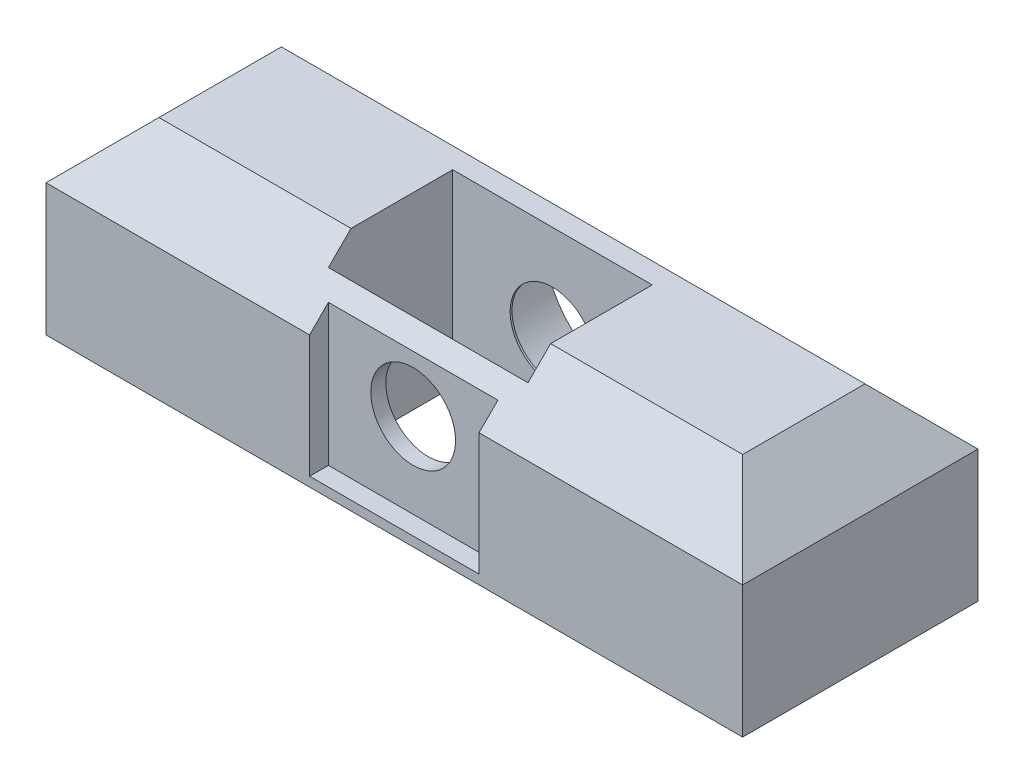
SolidWorks part; units mm, degrees
ref_plane "정면" through (0, 0, 0) normal (0, 0, 1) x (1, 0, 0)
ref_plane "윗면" through (0, 0, 0) normal (0, 1, 0) x (1, 0, 0)
ref_plane "우측면" through (0, 0, 0) normal (1, 0, 0) x (0, 0, -1)
sketch "스케치1" plane through (0, 0, 0) normal (0, 0, 1) x (1, 0, 0)
  line L1 (-18.5, 5) -> (18.5, 5)
  line L2 (-18.5, 5) -> (-18.5, -5)
  line L3 (-18.5, -5) -> (18.5, -5)
  line L4 (18.5, 5) -> (18.5, -5)
  line L5 (-18.5, 5) -> (18.5, -5) construction
  line L6 (-18.5, -5) -> (18.5, 5) construction
  point P0 (0, 0)
  dimension "D1" = 37
  dimension "D2" = 10
extrude "보스-돌출1" add sketch "스케치1" along normal blind 4.5
sketch "스케치4" plane through (0, 0, 4.5) normal (0, 0, 1) x (1, 0, 0)
  line L0 (-18.5, -5) -> (18.5, -5) construction
  line L1 (-18.5, 5) -> (-5.1, 5)
  line L2 (-18.5, 5) -> (-18.5, -5)
  line L3 (-18.5, -5) -> (-5.1, -5)
  line L4 (-5.1, 5) -> (-5.1, -5)
  line L5 (18.5, 5) -> (-18.5, 5) construction
  line L6 (18.5, 5) -> (5.1, 5)
  line L7 (18.5, 5) -> (18.5, -5)
  line L8 (18.5, -5) -> (5.1, -5)
  line L9 (5.1, 5) -> (5.1, -5)
  line L10 (18.5, -5) -> (18.5, 5) construction
  dimension "D1" = 10.2
  dimension "D2" = 5.1
extrude "보스-돌출2" add sketch "스케치4" along normal blind 6
sketch "스케치5" plane through (0, 0, 4.5) normal (0, 0, 1) x (1, 0, 0)
  line L1 (-5.1, -5) -> (5.1, -5)
  line L2 (-5.1, -5) -> (-5.1, 5)
  line L3 (-5.1, 5) -> (5.1, 5)
  line L4 (5.1, -5) -> (5.1, 5)
extrude "컷-돌출4" cut sketch "스케치5" against normal blind 0.2
sketch "스케치6" plane through (0, 0, 10.5) normal (0, 0, 1) x (1, 0, 0)
  line L1 (18.5, 5) -> (-18.5, 5)
  line L2 (18.5, 5) -> (18.5, -5)
  line L3 (18.5, -5) -> (-18.5, -5)
  line L4 (-18.5, 5) -> (-18.5, -5)
extrude "보스-돌출3" add sketch "스케치6" along normal blind 2
sketch "스케치2" plane through (0, 0, 0) normal (0, 0, 1) x (1, 0, 0)
  line L1 (-5.1, -5) -> (5.1, -5) construction
  circle A0 centre (0, 0) radius 2.25
  dimension "D1" = 5
  dimension "D2" = 4.5
extrude "컷-돌출1" cut sketch "스케치2" along normal through all
sketch "스케치3" plane through (0, 0, 0) normal (0, 0, -1) x (-1, 0, 0)
  circle A0 centre (0, 0) radius 4.5
extrude "컷-돌출3" cut sketch "스케치3" against normal blind 4
sketch "스케치7" plane through (0, 0, 12.5) normal (0, 0, 1) x (1, 0, 0)
  line L8 (-4.5, 4.5) -> (4.5, 4.5)
  line L9 (-4.5, 4.5) -> (-4.5, -4.5)
  line L10 (-4.5, -4.5) -> (4.5, -4.5)
  line L11 (4.5, 4.5) -> (4.5, -4.5)
  line L12 (-4.5, 4.5) -> (4.5, -4.5) construction
  line L13 (-4.5, -4.5) -> (4.5, 4.5) construction
  point P0 (0, 0)
  dimension "D1" = 9
  dimension "D2" = 9
extrude "컷-돌출5" cut sketch "스케치7" against normal blind 1
chamfer "모따기1" distance 3 angle 45 4 edges at (0, 5, 0) (0, 5, 12.5) (18.5, 5, 6.25) (-18.5, 5, 6.25)
sketch "스케치8" plane through (0, 5, 0) normal (0, 1, 0) x (1, 0, 0)
  line L0 (5.1, -4.3) -> (-5.1, -4.3) construction
  line L1 (-5.3, -4.1) -> (5.3, -4.1)
  line L2 (-5.3, -4.1) -> (-5.3, -10.7)
  line L3 (-5.3, -10.7) -> (5.3, -10.7)
  line L4 (5.3, -4.1) -> (5.3, -10.7)
  line L5 (-5.1, -9.5) -> (-5.1, -4.3) construction
  line L6 (5.1, -10.5) -> (-5.1, -10.5) construction
  line L7 (5.1, -9.5) -> (5.1, -4.3) construction
  dimension "D1" = 0.2
  dimension "D2" = 0.2
  dimension "D3" = 0.2
  dimension "D4" = 0.2
extrude "컷-돌출6" cut sketch "스케치8" against normal through all
